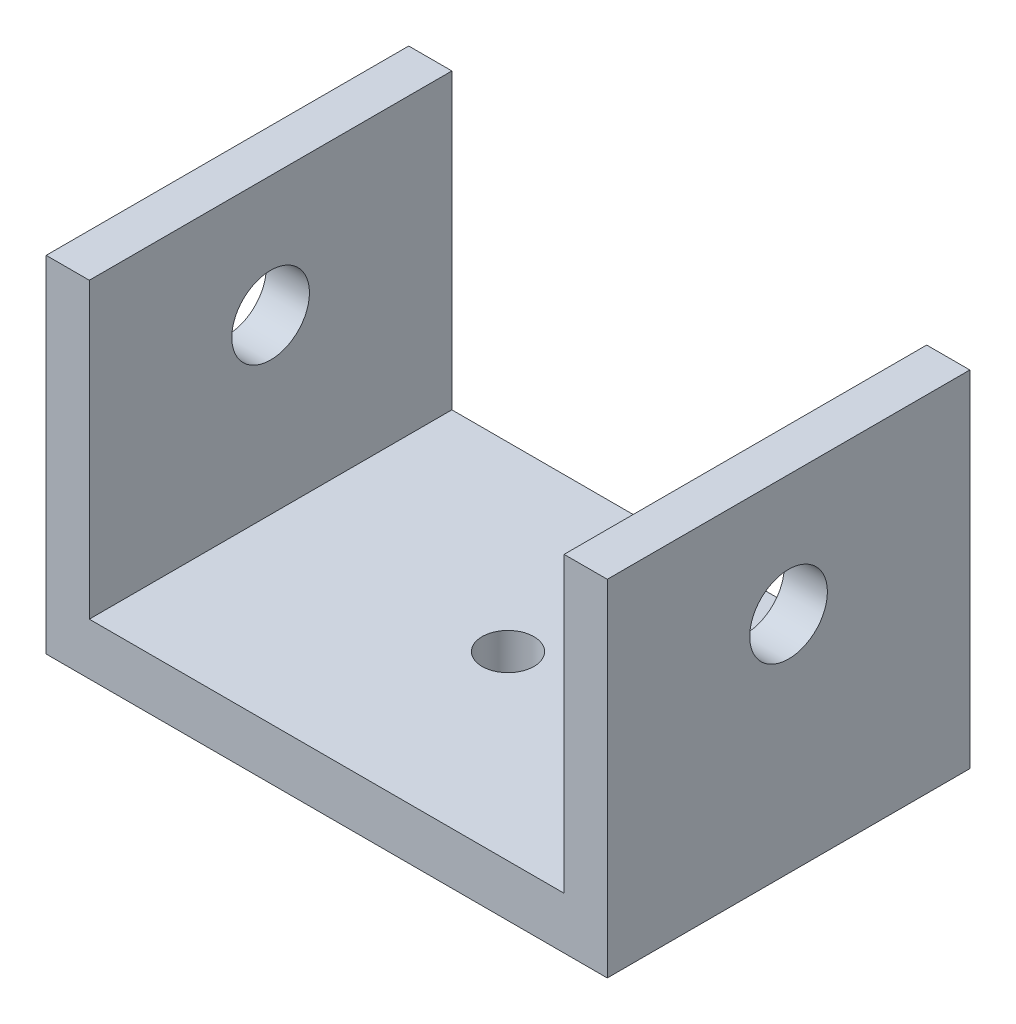
SolidWorks part; units mm, degrees
ref_plane "Front Plane" through (0, 0, 0) normal (0, 0, 1) x (1, 0, 0)
ref_plane "Top Plane" through (0, 0, 0) normal (0, 1, 0) x (1, 0, 0)
ref_plane "Right Plane" through (0, 0, 0) normal (1, 0, 0) x (0, 0, -1)
sketch "Sketch1" plane through (0, 0, 0) normal (0, 1, 0) x (1, 0, 0)
  line L0 (-13.75, 10.5) -> (-13.75, -10.5)
  line L1 (-16.25, -10.5) -> (16.25, -10.5)
  line L2 (-16.25, -10.5) -> (-16.25, 10.5)
  line L3 (-16.25, 10.5) -> (16.25, 10.5)
  line L4 (16.25, -10.5) -> (16.25, 10.5)
  line L5 (-16.25, -10.5) -> (16.25, 10.5) construction
  line L6 (-16.25, 10.5) -> (16.25, -10.5) construction
  line L7 (13.75, 10.5) -> (13.75, -10.5)
  point P0 (0, 0)
  dimension "D1" = 21
  dimension "D2" = 32.5
  dimension "D3" = 2.5
  dimension "D4" = 2.5
extrude "Boss-Extrude1" add sketch "Sketch1" along normal blind 3 contours L7 L3 L0 L1 region at (0, 0, 0)
extrude "Boss-Extrude2" add sketch "Sketch1<4>" along normal blind 20 contours L3 L2 L1 L0 | L3 L7 L1 L4 region at (-15, 0, 0) region at (15, 0, 0)
sketch "Sketch1<4>" plane through (0, 0, 0) normal (0, 1, 0) x (1, 0, 0) same geometry as "Sketch1"
sketch "Sketch2" plane through (16.25, 0, 0) normal (1, 0, 0) x (0, 0, -1)
  line L0 (-10.5, 20) -> (10.5, 20) construction
  circle A0 centre (0, 13) radius 2.25
  dimension "D1" = 4.5
  dimension "D2" = 7
extrude "Cut-Extrude1" cut sketch "Sketch2" against normal through all
sketch "Sketch3" plane through (0, 3, 0) normal (0, 1, 0) x (1, 0, 0)
  circle A0 centre (0, 0) radius 1.5
  dimension "D1" = 3
extrude "Cut-Extrude2" cut sketch "Sketch3" against normal through all
